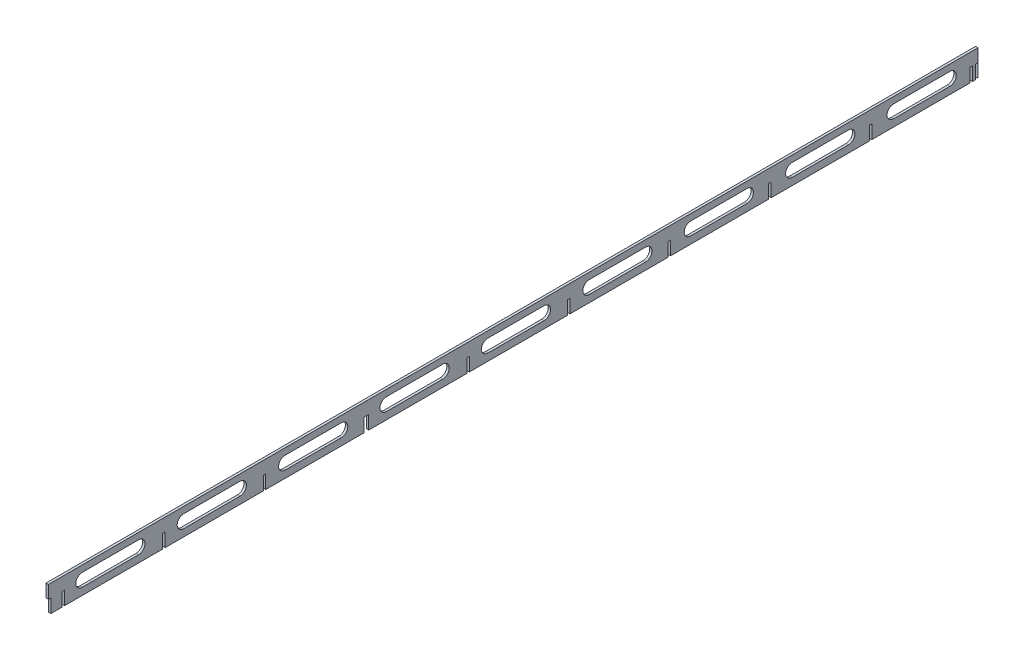
SolidWorks part; units mm, degrees
material "轻木"
ref_plane "前视基准面" through (0, 0, 0) normal (0, 0, 1) x (1, 0, 0)
ref_plane "上视基准面" through (0, 0, 0) normal (0, 1, 0) x (1, 0, 0)
ref_plane "右视基准面" through (0, 0, 0) normal (1, 0, 0) x (0, 0, -1)
other "Configuration Table"
sketch "草图1" plane through (0, 0, 0) normal (0, 0, 1) x (1, 0, 0)
  line L1 (-44.1255, 21.6473) -> (-47.1255, 21.6473)
  line L2 (-44.1255, 21.6473) -> (-44.1255, -11.2586)
  line L3 (-44.1255, -11.2586) -> (-47.1255, -11.2586)
  line L4 (-47.1255, 21.6473) -> (-47.1255, -11.2586)
  dimension "D1" = 3
extrude "凸台-拉伸1" add sketch "草图1" along normal blind 1155
sketch "草图2" plane through (-47.1255, 0, 0) normal (-1, 0, 0) x (0, 0, 1)
  line L0 (1155, -11.2586) -> (0, -11.2586) construction
  line L1 (7.01, -11.2586) -> (10.01, -11.2586)
  line L2 (7.01, -11.2586) -> (7.01, 5.5696)
  line L3 (7.01, 5.5696) -> (10.01, 5.5696)
  line L4 (10.01, -11.2586) -> (10.01, 5.5696)
  line L6 (132.01, -11.2586) -> (135.01, -11.2586)
  line L7 (132.01, -11.2586) -> (132.01, 5.5696)
  line L8 (132.01, 5.5696) -> (135.01, 5.5696)
  line L9 (135.01, -11.2586) -> (135.01, 5.5696)
  line L10 (257.01, -11.2586) -> (260.01, -11.2586)
  line L11 (257.01, -11.2586) -> (257.01, 5.5696)
  line L12 (257.01, 5.5696) -> (260.01, 5.5696)
  line L13 (260.01, -11.2586) -> (260.01, 5.5696)
  line L14 (382.01, -11.2586) -> (385.01, -11.2586)
  line L15 (382.01, -11.2586) -> (382.01, 5.5696)
  line L16 (382.01, 5.5696) -> (385.01, 5.5696)
  line L17 (385.01, -11.2586) -> (385.01, 5.5696)
  line L18 (507.01, -11.2586) -> (510.01, -11.2586)
  line L19 (507.01, -11.2586) -> (507.01, 5.5696)
  line L20 (507.01, 5.5696) -> (510.01, 5.5696)
  line L21 (510.01, -11.2586) -> (510.01, 5.5696)
  line L22 (632.01, -11.2586) -> (635.01, -11.2586)
  line L23 (632.01, -11.2586) -> (632.01, 5.5696)
  line L24 (632.01, 5.5696) -> (635.01, 5.5696)
  line L25 (635.01, -11.2586) -> (635.01, 5.5696)
  line L30 (7.01, -11.2586) -> (132.01, -11.2586) construction
  line L31 (1152.01, 5.5696) -> (1155.01, 5.5696)
  line L32 (3.01, -11.2586) -> (0.01, -11.2586)
  line L33 (3.01, -11.2586) -> (3.01, 5.5696)
  line L34 (3.01, 5.5696) -> (0.01, 5.5696)
  line L35 (0.01, -11.2586) -> (0.01, 5.5696)
  line L36 (1152.01, 5.5696) -> (1152.01, -11.2586)
  line L37 (1152.01, -11.2586) -> (1155.01, -11.2586)
  line L38 (1155.01, 5.5696) -> (1155.01, -11.2586)
  line L39 (763.01, -11.2586) -> (760.01, -11.2586)
  line L40 (763.01, -11.2586) -> (763.01, 5.5696)
  line L41 (763.01, 5.5696) -> (760.01, 5.5696)
  line L42 (760.01, -11.2586) -> (760.01, 5.5696)
  line L43 (888.01, -11.2586) -> (885.01, -11.2586)
  line L44 (888.01, -11.2586) -> (888.01, 5.5696)
  line L45 (888.01, 5.5696) -> (885.01, 5.5696)
  line L46 (885.01, -11.2586) -> (885.01, 5.5696)
  line L47 (1013.01, -11.2586) -> (1010.01, -11.2586)
  line L48 (1013.01, -11.2586) -> (1013.01, 5.5696)
  line L49 (1013.01, 5.5696) -> (1010.01, 5.5696)
  line L50 (1010.01, -11.2586) -> (1010.01, 5.5696)
  line L51 (1138.01, -11.2586) -> (1135.01, -11.2586)
  line L52 (1138.01, -11.2586) -> (1138.01, 5.5696)
  line L53 (1138.01, 5.5696) -> (1135.01, 5.5696)
  line L54 (1135.01, -11.2586) -> (1135.01, 5.5696)
  line L55 (763.01, -11.2586) -> (888.01, -11.2586) construction
  line L61 (35, 5.6473) -> (105, 5.6473) construction
  line L62 (35, 13.6473) -> (105, 13.6473)
  line L63 (760.01, 5.5696) -> (757.01, 5.5696)
  line L64 (757.01, 5.5696) -> (757.01, -11.2586)
  line L66 (757.01, -11.2586) -> (760.01, -11.2586)
  line L67 (35, -2.3527) -> (105, -2.3527)
  line L68 (757.01, 5.5696) -> (760.01, 5.5696)
  line L69 (1155, 21.6473) -> (0, 21.6473) construction
  line L70 (0, 21.6473) -> (0, -11.2586) construction
  line L71 (161, 5.6473) -> (231, 5.6473) construction
  line L72 (161, 13.6473) -> (231, 13.6473)
  line L73 (161, -2.3527) -> (231, -2.3527)
  line L74 (287, 5.6473) -> (357, 5.6473) construction
  line L75 (287, 13.6473) -> (357, 13.6473)
  line L76 (287, -2.3527) -> (357, -2.3527)
  line L77 (413, 5.6473) -> (483, 5.6473) construction
  line L78 (413, 13.6473) -> (483, 13.6473)
  line L79 (413, -2.3527) -> (483, -2.3527)
  line L80 (539, 5.6473) -> (609, 5.6473) construction
  line L81 (539, 13.6473) -> (609, 13.6473)
  line L82 (539, -2.3527) -> (609, -2.3527)
  line L83 (665, 5.6473) -> (735, 5.6473) construction
  line L84 (665, 13.6473) -> (735, 13.6473)
  line L85 (665, -2.3527) -> (735, -2.3527)
  line L86 (791, 5.6473) -> (861, 5.6473) construction
  line L87 (791, 13.6473) -> (861, 13.6473)
  line L88 (791, -2.3527) -> (861, -2.3527)
  line L89 (917, 5.6473) -> (987, 5.6473) construction
  line L90 (917, 13.6473) -> (987, 13.6473)
  line L91 (917, -2.3527) -> (987, -2.3527)
  line L92 (1043, 5.6473) -> (1113, 5.6473) construction
  line L93 (1043, 13.6473) -> (1113, 13.6473)
  line L94 (1043, -2.3527) -> (1113, -2.3527)
  line L95 (757.01, -11.2586) -> (760.01, -11.2586)
  line L98 (35, 5.6473) -> (161, 5.6473) construction
  line L99 (760.01, -11.2586) -> (757.01, -11.2586)
  arc A0 (35, 13.6473) -> (35, -2.3527) centre (35, 5.6473) ccw
  arc A1 (105, -2.3527) -> (105, 13.6473) centre (105, 5.6473) ccw
  arc A2 (161, 13.6473) -> (161, -2.3527) centre (161, 5.6473) ccw
  arc A3 (231, -2.3527) -> (231, 13.6473) centre (231, 5.6473) ccw
  arc A4 (287, 13.6473) -> (287, -2.3527) centre (287, 5.6473) ccw
  arc A5 (357, -2.3527) -> (357, 13.6473) centre (357, 5.6473) ccw
  arc A6 (413, 13.6473) -> (413, -2.3527) centre (413, 5.6473) ccw
  arc A7 (483, -2.3527) -> (483, 13.6473) centre (483, 5.6473) ccw
  arc A8 (539, 13.6473) -> (539, -2.3527) centre (539, 5.6473) ccw
  arc A9 (609, -2.3527) -> (609, 13.6473) centre (609, 5.6473) ccw
  arc A10 (665, 13.6473) -> (665, -2.3527) centre (665, 5.6473) ccw
  arc A11 (735, -2.3527) -> (735, 13.6473) centre (735, 5.6473) ccw
  arc A12 (791, 13.6473) -> (791, -2.3527) centre (791, 5.6473) ccw
  arc A13 (861, -2.3527) -> (861, 13.6473) centre (861, 5.6473) ccw
  arc A14 (917, 13.6473) -> (917, -2.3527) centre (917, 5.6473) ccw
  arc A15 (987, -2.3527) -> (987, 13.6473) centre (987, 5.6473) ccw
  arc A16 (1043, 13.6473) -> (1043, -2.3527) centre (1043, 5.6473) ccw
  arc A17 (1113, -2.3527) -> (1113, 13.6473) centre (1113, 5.6473) ccw
  point P74 (70, 5.6473)
  point P89 (196, 5.6473)
  point P96 (322, 5.6473)
  point P103 (448, 5.6473)
  point P110 (574, 5.6473)
  point P117 (700, 5.6473)
  point P124 (826, 5.6473)
  point P131 (952, 5.6473)
  point P138 (1078, 5.6473)
  line M3 (0, -11.2586) -> (1155, -11.2586)
  line M4 (1155, -11.2586) -> (1155, 21.6473)
  dimension "D5" = 8
  dimension "D2" = 125
  dimension "D3" = 125
  dimension "D4" = 16
  dimension "D6" = 70
  dimension "D7" = 70
  dimension "D8" = 126
  dimension "D11" = 3
  dimension "D12" = 3
  dimension "D13" = 16.8282
  dimension "D14" = 7
  dimension "D15" = 3
  dimension "D16" = 125
  dimension "D17" = 17
  dimension "D18" = 3
  dimension "D1" = 6
  dimension "D10" = 4
  dimension "D9" = 9
extrude "切除-拉伸1" cut sketch "草图2" against normal blind 3 contours L35 L33 L34 M3 | L4 L3 L2 M3 | L67 A1 L62 A0 | L9 L8 L7 M3 | L73 A3 L72 A2 | L13 L12 L11 M3 | L76 A5 L75 A4 | L17 L16 L15 M3 | L79 A7 L78 A6 | L21 L20 L19 M3 | L82 A9 L81 A8 | L25 L24 L23 M3 | L85 A11 L84 A10 | L63 L64 L42 M3 | L42 L40 L41 M3 | L88 A13 L87 A12 | L46 L44 L45 M3 | L91 A15 L90 A14 | L50 L48 L49 M3 | L94 A17 L93 A16 | L54 L52 L53 M3 | L31 L36 M3 M4 region at (-47.1255, -2.8445, 8.51) region at (-47.1255, -2.8445, 1153.505) region at (-47.1255, -2.8445, 1136.51) region at (-47.1255, -2.8445, 1011.51) region at (-47.1255, -2.8445, 886.51) region at (-47.1255, -2.8445, 758.51) region at (-47.1255, -2.8445, 633.51) region at (-47.1255, -2.8445, 508.51) region at (-47.1255, -2.8445, 383.51) region at (-47.1255, -2.8445, 258.51) region at (-47.1255, -2.8445, 133.51) region at (-47.1255, -2.8445, 1.51) region at (-47.1255, -2.8445, 761.51) region at (-47.1255, 5.6473, 70) region at (-47.1255, 5.6473, 196) region at (-47.1255, 5.6473, 322) region at (-47.1255, 5.6473, 448) region at (-47.1255, 5.6473, 574) region at (-47.1255, 5.6473, 700) region at (-47.1255, 5.6473, 826) region at (-47.1255, 5.6473, 952) region at (-47.1255, 5.6473, 1078)
